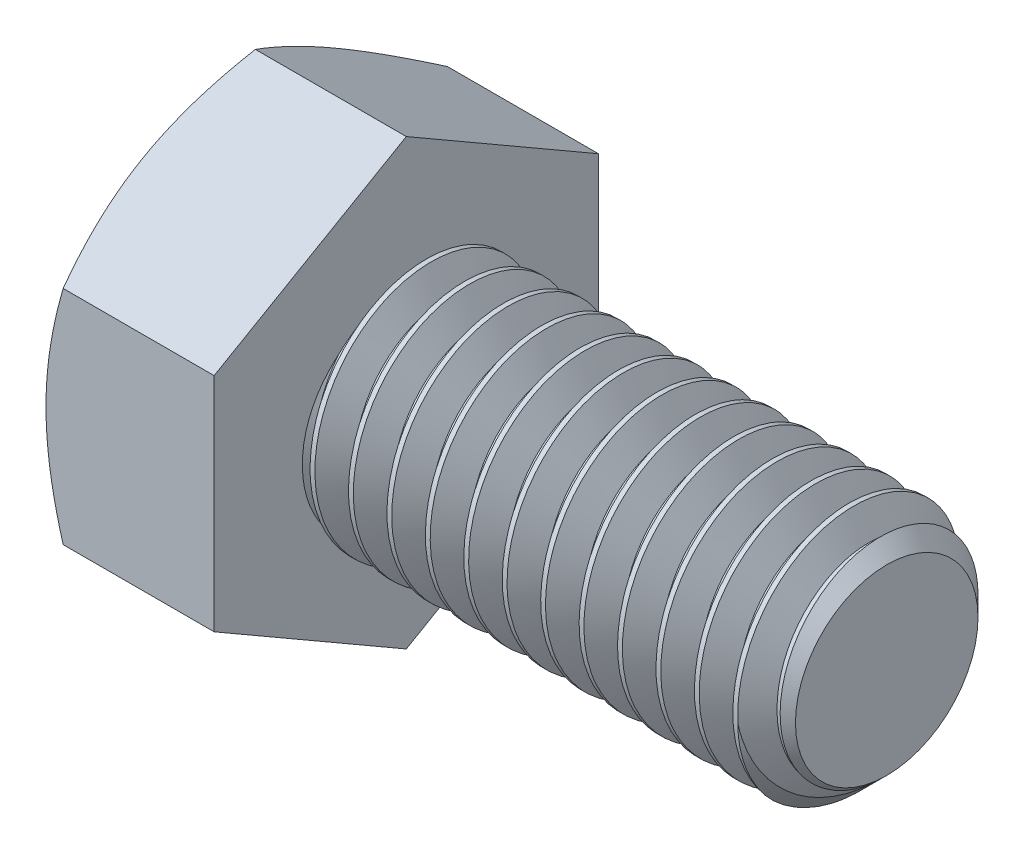
SolidWorks part; units mm, degrees
ref_plane "Front Plane" through (0, 0, 0) normal (0, 0, 1) x (1, 0, 0)
ref_plane "Top Plane" through (0, 0, 0) normal (0, 1, 0) x (1, 0, 0)
ref_plane "Right Plane" through (0, 0, 0) normal (1, 0, 0) x (0, 0, -1)
sketch "Sketch1" plane through (0, 0, 0) normal (0, 0, 1) x (1, 0, 0)
  line L0 (-6.75, 0) -> (6.75, 0) construction
  line L1 (-3.25, 4) -> (-3.25, -4) construction
  line L2 (-6.75, 4) -> (-6.75, -4) construction
  line L3 (6.75, 2.5) -> (6.75, -2.5) construction
  point P8 (3.95, -2.5)
  dimension "Thread Dia" = 5
  dimension "Hex" = 8
  dimension "Head Ht" = 3.5
  dimension "Length" = 10
  dimension "D1" = 2.8
ref_plane "Plane2" through (6.75, 0, 0) normal (1, 0, 0) x (0, 0, -1)
sketch "Sketch2" plane through (6.75, 0, 0) normal (1, 0, 0) x (0, 0, -1)
  circle A0 centre (0, 0) radius 2.5
extrude "Boss-Extrude1" add sketch "Sketch2" against normal up to vertex (10 mm away) up to point (-3.25, -4, 0)
sketch "Sketch4" plane through (6.75, 0, 0) normal (1, 0, 0) x (0, 0, -1)
  circle A1 centre (0, 0) radius 2.5
  circle A2 centre (0, 0) radius 2.5
  dimension "D1" = 0
curve "Helix/Spiral1" pitch 0.8 height 10.8 turns 13.5 parameters "Pitch"=0.8
chamfer "Chamfer1" distance 0.6 angle 45 1 edges at (6.75, 0, -2.5)
sketch "Sketch5" plane through (0, 0, 0) normal (0, 0, 1) x (1, 0, 0)
  line L0 (6.75, 2.5) -> (7.05, 1.9804)
  line L1 (7.05, 1.9804) -> (7.15, 1.9804)
  line L2 (7.15, 1.9804) -> (7.45, 2.5)
  line L3 (6.75, 2.5) -> (7.45, 2.5)
  line L4 (7.1, 1.9804) -> (7.1, 2.5) construction
  line L5 (6.9, 2.2402) -> (7.3, 2.2402) construction
  line L6 (6.75, -2.5) -> (6.75, 2.5) construction
  dimension "D1" = 60
  dimension "D2" = 0.1
  dimension "D3" = 0.4
sweep "Cut-Sweep1" cut profiles "Sketch5" path "Helix/Spiral1" align with end faces yes
sketch "Sketch3" plane through (-3.25, 0, 0) normal (-1, 0, 0) x (0, 0, 1)
  line L0 (0, 4) -> (0, -4) construction
  line L1 (-4, -2.3094) -> (0, -4.6188)
  line L2 (0, -4.6188) -> (4, -2.3094)
  line L3 (4, -2.3094) -> (4, 2.3094)
  line L4 (4, 2.3094) -> (0, 4.6188)
  line L5 (0, 4.6188) -> (-4, 2.3094)
  line L6 (-4, 2.3094) -> (-4, -2.3094)
  circle A0 centre (0, 0) radius 4 construction
extrude "Boss-Extrude2" add sketch "Sketch3" along normal up to vertex (3.5 mm away) up to point (-6.75, -4, 0)
sketch "Sketch6" plane through (-6.75, 0, 0) normal (-1, 0, 0) x (0, 0, 1)
  circle A0 centre (0, 0) radius 4 construction
  circle A1 centre (0, 0) radius 4
extrude "Cut-Extrude1" cut sketch "Sketch6" against normal through all draft 60 flip side to cut
sketch "Sketch9" plane through (0, 0, 0) normal (0, 0, 1) x (1, 0, 0)
  line L0 (-3.25, 2.5) -> (-3.25, 0)
  line L1 (-3.25, 0) -> (-44.75, 0)
  line L2 (-44.75, 0) -> (-47.25, 2.5)
  line L3 (-47.25, 2.5) -> (-3.25, 2.5)
  line L4 (-6.75, 0) -> (6.75, 0) construction
  line L5 (-3.25, 4) -> (-3.25, -4) construction
  line L6 (6.75, 2.5) -> (6.75, -2.5) construction
  dimension "D1" = 45
  dimension "MinThreadLg" = 54
revolve "Revolve1" [suppressed] add sketch "Sketch9" angle 360 about L1
equation "\"D2@Sketch5\" = \"Pitch@Helix/Spiral1\"*.125"
equation "\"D3@Sketch5\" = \"Pitch@Helix/Spiral1\"*.50"
equation "\"D3@Helix/Spiral1\" = \"Length@Sketch1\"+\"Pitch@Helix/Spiral1\""
equation "\"D1@Chamfer1\" = \"Pitch@Helix/Spiral1\"*.750"
equation "\"D1@Sketch1\" = \"Pitch@Helix/Spiral1\"*3.50"
